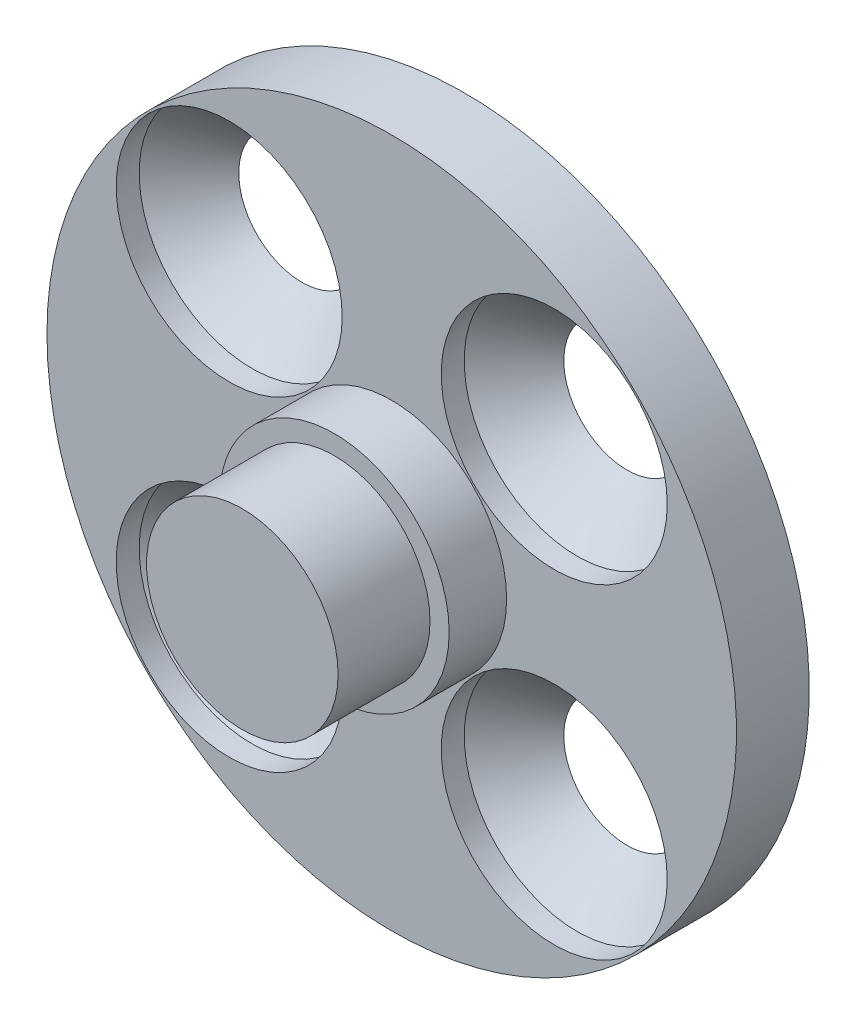
SolidWorks part; units mm, degrees
ref_plane "Front Plane" through (0, 0, 0) normal (1, 0, 0) x (0, 1, 0)
ref_plane "Top Plane" through (0, 0, 0) normal (0, 0, 1) x (0, 1, 0)
ref_plane "Right Plane" through (0, 0, 0) normal (0, 1, 0) x (-1, 0, 0)
ref_axis "x axis" through (-88.99, 0, 0) along (1, 0, 0)
ref_axis "y xxis" through (0, 88.99, 0) along (0, -1, 0)
ref_axis "z axis" through (0, 0, 55) along (0, 0, -1)
sketch "Sketch1" plane through (0, 0, 0) normal (0, 0, 1) x (0, 1, 0)
  line L1 (-4.2426, -4.2426) -> (4.2426, -4.2426) construction
  line L2 (-4.2426, -4.2426) -> (-4.2426, 4.2426) construction
  line L3 (-4.2426, 4.2426) -> (4.2426, 4.2426) construction
  line L4 (4.2426, -4.2426) -> (4.2426, 4.2426) construction
  line L5 (-4.2426, -4.2426) -> (4.2426, 4.2426) construction
  line L6 (-4.2426, 4.2426) -> (4.2426, -4.2426) construction
  circle A3 centre (0, 0) radius 9
  circle A4 centre (-4.2426, 4.2426) radius 1.55
  circle A5 centre (4.2426, 4.2426) radius 1.55
  circle A6 centre (4.2426, -4.2426) radius 1.55
  circle A7 centre (-4.2426, -4.2426) radius 1.55
  dimension "D1" = 18
  dimension "D2" = 12
  dimension "D3" = 3.1
extrude "Boss-Extrude1" add sketch "Sketch1" along normal blind 1.9
sketch "Sketch2" plane through (0, 0, 1.9) normal (0, 0, 1) x (1, 0, 0)
  circle A0 centre (0, 0) radius 3
  dimension "D1" = 6
extrude "Boss-Extrude2" add sketch "Sketch2" along normal blind 1.5
sketch "Sketch3" plane through (0, 0, 3.4) normal (0, 0, 1) x (1, 0, 0)
  circle A0 centre (0, 0) radius 2.5
  dimension "D1" = 5
extrude "Boss-Extrude3" add sketch "Sketch3" along normal blind 2.4
sketch "Sketch4" plane through (0, 0, 1.9) normal (0, 0, 1) x (1, 0, 0)
  circle A0 centre (-4.2426, 4.2426) radius 2.95
  circle A1 centre (4.2426, 4.2426) radius 2.95
  circle A2 centre (4.2426, -4.2426) radius 2.95
  circle A3 centre (-4.2426, -4.2426) radius 2.95
  dimension "D1" = 5.9
extrude "Cut-Extrude1" cut sketch "Sketch4" against normal blind 0.6
chamfer "Chamfer1" distance 1.4 angle 45 4 edges at (-2.6926, -4.2426, 1.3) (5.7926, -4.2426, 1.3) (5.7926, 4.2426, 1.3) (-2.6926, 4.2426, 1.3)
